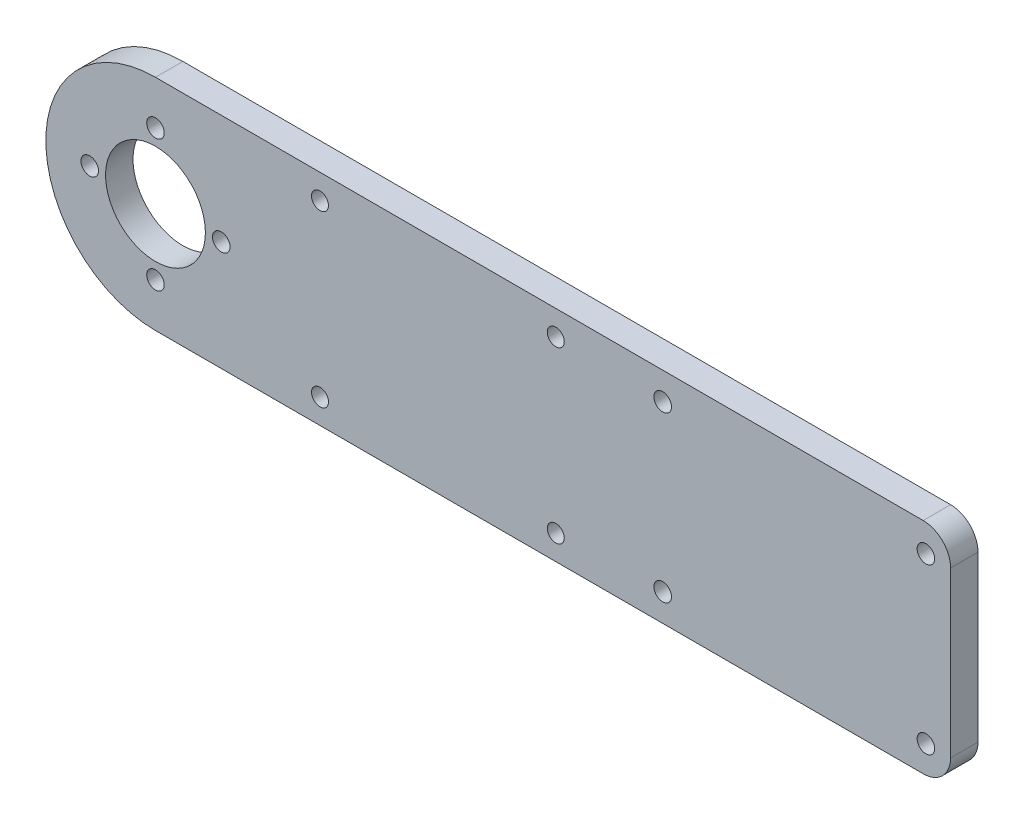
SolidWorks part; units mm, degrees
material "Acrylic (Medium-high impact)"
ref_plane "Front Plane" through (0, 0, 0) normal (0, 0, 1) x (1, 0, 0)
ref_plane "Top Plane" through (0, 0, 0) normal (0, 1, 0) x (1, 0, 0)
ref_plane "Right Plane" through (0, 0, 0) normal (1, 0, 0) x (0, 0, -1)
sketch "Sketch2" plane through (0, 0, 0) normal (0, 0, 1) x (1, 0, 0)
  line L0 (0, 20) -> (0, -20)
  line L1 (0, 20) -> (145, 20)
  line L2 (0, -20) -> (145, -20)
  line L3 (145, 20) -> (145, -20)
  line L4 (0, 0) -> (-20, 0)
  circle A0 centre (0, 0) radius 20
  circle A1 centre (0, 0) radius 9.1
  dimension "D1" = 40
  dimension "D3" = 18.2
  dimension "D2" = 165
extrude "Boss-Extrude1" add sketch "Sketch2" along normal mid plane 5 contours A1 L0 A0 | A0 L2 L3 L1 | A1 L4 A0 L0 | A1 L0 A0 L4 region at (9.696, 0, 0) region at (80.2769, 0, 0) region at (-9.696, 9.696, 0) region at (-9.696, -9.696, 0)
fillet "Fillet1" radius 5 2 edges at (145, -20, 0) (145, 20, 0)
sketch "Sketch3" plane through (0, 0, -2.5) normal (0, 0, -1) x (-1, 0, 0)
  line L0 (-51.5, 20) -> (-51.5, -20)
  line L1 (-51.5, 0) -> (-30, 0)
  line L2 (-30, 0) -> (-30, 15.5)
  line L3 (-145, 15) -> (-145, -15)
  line L4 (-140, -20) -> (0, -20)
  line L5 (0, 20) -> (-140, 20)
  line L6 (-145, 15) -> (-145, -15)
  line L7 (-140, -20) -> (0, -20)
  line L8 (0, 20) -> (-140, 20)
  line L9 (-51.5, 0) -> (-116.5, 0)
  line L10 (-116.5, 0) -> (-116.5, 15)
  line L11 (-116.5, 15) -> (-140.5, 15)
  line L12 (0, 0) -> (0, 12)
  circle A0 centre (0, 0) radius 12
  circle A1 centre (-30, 15.5) radius 1.55
  circle A2 centre (-30, -15.5) radius 1.55
  arc A3 (-145, -15) -> (-140, -20) centre (-140, -15) ccw
  arc A4 (0, -20) -> (0, 20) centre (0, 0) ccw
  arc A5 (-140, 20) -> (-145, 15) centre (-140, 15) ccw
  arc A6 (-145, -15) -> (-140, -20) centre (-140, -15) ccw
  arc A7 (0, -20) -> (0, 20) centre (0, 0) ccw
  arc A8 (-140, 20) -> (-145, 15) centre (-140, 15) ccw
  circle A9 centre (-73, -15.5) radius 1.55
  circle A10 centre (-73, 15.5) radius 1.55
  circle A11 centre (-140.5, 15) radius 1.6
  circle A12 centre (-140.5, -15) radius 1.6
  circle A13 centre (-92.5, -15) radius 1.6
  circle A14 centre (-92.5, 15) radius 1.6
  circle A15 centre (0, 12) radius 1.6
  circle A16 centre (12, 0) radius 1.6
  circle A17 centre (0, -12) radius 1.6
  circle A18 centre (-12, 0) radius 1.6
  point P35 (0, 0)
  dimension "D2" = 24
  dimension "D6" = 3.1
  dimension "D10" = 3.2
  dimension "D11" = 3.2
  dimension "D3" = 21.5
  dimension "D4" = 15.5
  dimension "D5" = 30
  dimension "D7" = 65
  dimension "D8" = 15
  dimension "D9" = 24
  dimension "D1" = 0
  dimension "D12" = 4
extrude "Cut-Extrude1" cut sketch "Sketch3" against normal through all contours A14 | A13 | A11 | A12 | A0 A16 | A0 A16 | A0 A17 | A2 | A9 | A10 | A1 | A18 | A15 | A17 region at (142.0547, 15, -2.5) region at (-12.6595, 0, -2.5) region at (-11.3021, 0, -2.5) region at (0, -12.6595, -2.5) region at (140.5, -15, -2.5) region at (92.5, -15, -2.5) region at (92.5, 15, -2.5)
